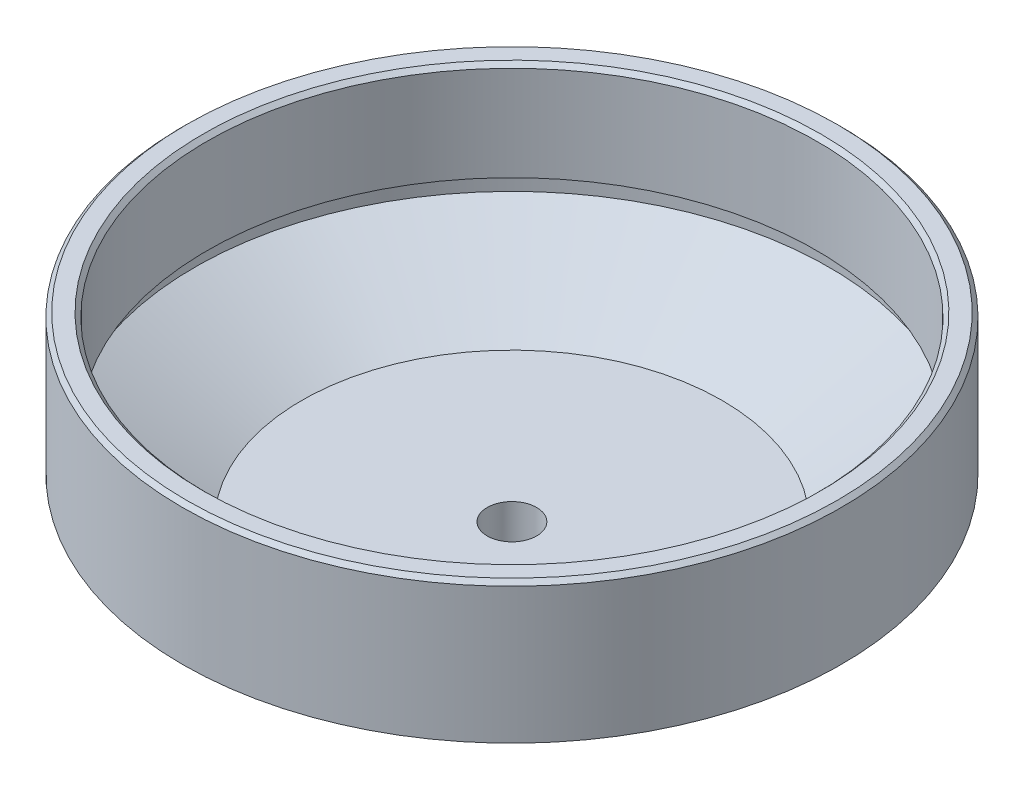
SolidWorks part; units mm, degrees
material "AISI 304"
ref_plane "Спереди" through (0, 0, 0) normal (0, 0, 1) x (1, 0, 0)
ref_plane "Сверху" through (0, 0, 0) normal (0, 1, 0) x (1, 0, 0)
ref_plane "Справа" through (0, 0, 0) normal (1, 0, 0) x (0, 0, -1)
ref_axis "ОсьX" through (-88.99, 0, 0) along (1, 0, 0)
ref_axis "ОсьZ" through (0, 55, 0) along (0, -1, 0)
ref_axis "ОсьY" through (0, 0, -88.99) along (0, 0, 1)
sketch "Эскиз1" plane through (0, 0, 0) normal (0, 0, 1) x (1, 0, 0)
  line L0 (-40, 28) -> (-40, 11)
  line L1 (0, 26.169) -> (0, -22.1581) construction
  line L2 (-20.9474, 0) -> (-3, 0)
  line L3 (-3, 0) -> (-3, 6)
  line L4 (-3, 6) -> (-25.5096, 6)
  line L5 (-38.5, 13.5) -> (-38.5, 16)
  line L6 (-38.5, 16) -> (-37, 16)
  line L7 (-37, 16) -> (-37, 28)
  line L8 (-37, 28) -> (-40, 28)
  line L11 (-40, 11) -> (-20.9474, 0)
  line L12 (-38.5, 13.5) -> (-25.5096, 6)
  dimension "D1" = 80
  dimension "D2" = 60
  dimension "D3" = 74
  dimension "D4" = 6
  dimension "D5" = 6
  dimension "D6" = 17
  dimension "D7" = 1.5
  dimension "D8" = 2.5
  dimension "D9" = 12
  dimension "D10" = 28
revolve "Повернуть1" add sketch "Эскиз1" angle 360 mid plane about L1
cosmetic thread "Условное изображение резьбы1" parameters "D2"=76
cosmetic thread "Условное изображение резьбы2" parameters "D2"=8
chamfer "Фаска1" distance 0.5 angle 45 3 edges at (0, 0, 3) (0, 28, 40) (0, 28, 37)
